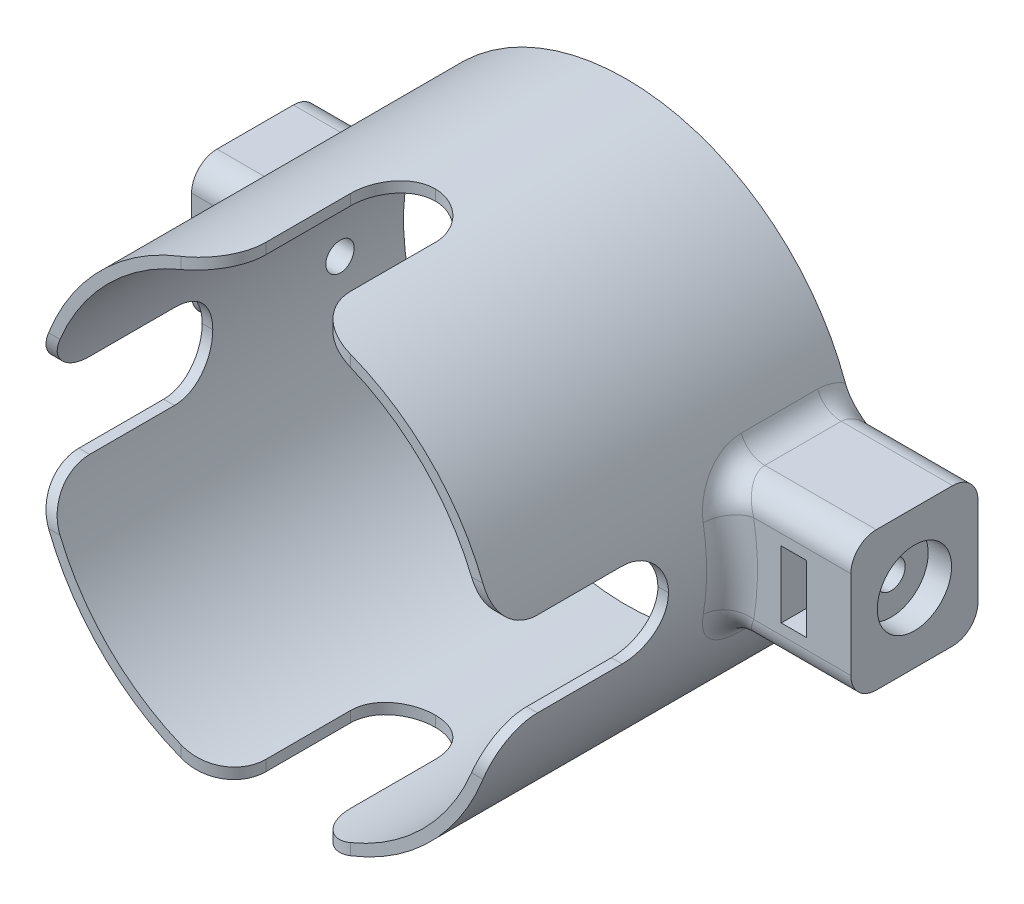
SolidWorks part; units mm, degrees
ref_plane "Front Plane" through (0, 0, 0) normal (0, 0, 1) x (1, 0, 0)
ref_plane "Top Plane" through (0, 0, 0) normal (0, 1, 0) x (1, 0, 0)
ref_plane "Right Plane" through (0, 0, 0) normal (1, 0, 0) x (0, 0, -1)
sketch "Sketch2" plane through (0, 0, 0) normal (0, 0, 1) x (1, 0, 0)
  circle A0 centre (0, 0) radius 66.675
  circle A1 centre (0, 0) radius 69.85
  dimension "D1" = 133.35
  dimension "D2" = 139.7
extrude "Boss-Extrude1" add sketch "Sketch2" along normal mid plane 177.8
sketch "Sketch6" plane through (0, 0, 0) normal (0, 0, 1) x (1, 0, 0)
  line L0 (66.675, -20.8199) -> (66.675, 20.8199)
  line L1 (66.675, 20.8199) -> (92.075, 20.8199)
  line L2 (92.075, 20.8199) -> (92.075, -20.8199)
  line L3 (92.075, 0) -> (66.675, 0) construction
  line L4 (66.675, -20.8199) -> (92.075, -20.8199)
  line L5 (0, 0) -> (0, 66.675) construction
  line L6 (-66.675, 20.8199) -> (-92.075, 20.8199)
  line L7 (-66.675, -20.8199) -> (-66.675, 20.8199)
  line L8 (-66.675, -20.8199) -> (-92.075, -20.8199)
  line L9 (-92.075, 20.8199) -> (-92.075, -20.8199)
  circle A0 centre (0, 0) radius 66.675 construction
  circle A1 centre (0, 0) radius 69.85 construction
  dimension "D1" = 25.4
extrude "Boss-Extrude2" add sketch "Sketch6" along normal mid plane 38.1
sketch "Sketch12" plane through (92.075, 0, 0) normal (1, 0, 0) x (0, 0, -1)
  line L1 (-19.05, 20.8199) -> (-19.05, -20.8199) construction
  line L4 (-19.05, 10) -> (19.05, 10)
  line L5 (19.05, -20.8199) -> (19.05, 20.8199) construction
  line L6 (19.05, 10) -> (19.05, -10)
  line L7 (19.05, -10) -> (-19.05, -10)
  line L8 (0, 10) -> (0, -10) construction
  line L9 (-19.05, 10) -> (-19.05, -10)
  dimension "D1" = 20
extrude "Cut-Extrude1" cut sketch "Sketch12" against normal blind 7.5
sketch "Sketch17" plane through (92.075, 0, 0) normal (1, 0, 0) x (0, 0, -1)
  line L0 (-19.05, 20.8199) -> (19.05, 20.8199)
  line L1 (19.05, 20.8199) -> (19.05, -20.8199)
  line L2 (19.05, -20.8199) -> (-19.05, -20.8199)
  line L3 (-19.05, -20.8199) -> (-19.05, 20.8199)
extrude "Boss-Extrude5" add sketch "Sketch17" along normal blind 6.35
sketch "Sketch18" plane through (98.425, 0, 0) normal (1, 0, 0) x (0, 0, -1)
  line L4 (-19.05, 20.8199) -> (-19.05, -20.8199)
  line L5 (-19.05, -20.8199) -> (19.05, -20.8199)
  line L6 (19.05, -20.8199) -> (19.05, 20.8199)
  line L7 (19.05, 20.8199) -> (-19.05, 20.8199)
  line L8 (-19.05, 20.8199) -> (-19.05, -20.8199)
  line L9 (-19.05, -20.8199) -> (19.05, -20.8199)
  line L10 (19.05, -20.8199) -> (19.05, 20.8199)
  line L11 (19.05, 20.8199) -> (-19.05, 20.8199)
  circle A0 centre (0, 0) radius 11.125
  dimension "D1" = 22.25
  dimension "D2" = 0
extrude "Boss-Extrude6" add sketch "Sketch18" along normal blind 7
sketch "Sketch19" plane through (0, 0, 0) normal (1, 0, 0) x (0, 0, -1)
  circle A0 centre (0, 0) radius 4.25
  dimension "D1" = 8.5
extrude "Cut-Extrude5" cut sketch "Sketch19" against normal through all both and the other way through all
mirror "Mirror6" [suppressed] about plane through (0, 0, 0) normal (1, 0, 0)
fillet "Fillet3" radius 7.62 16 edges at (66.675, -20.8199, 0) (69.85, 0, -19.05) (66.675, 20.8199, 0) (69.85, 0, 19.05) (-69.85, 0, -19.05) (-66.675, -20.8199, 0) (-69.85, 0, 19.05) (-66.675, 20.8199, 0) (86.05, -20.8199, 19.05) (86.05, -20.8199, -19.05) (86.05, 20.8199, -19.05) (86.05, 20.8199, 19.05) (-79.375, 20.8199, 19.05) (-79.375, -20.8199, 19.05) (-79.375, -20.8199, -19.05) (-79.375, 20.8199, -19.05)
sketch "Sketch21" plane through (0, 0, 0) normal (1, 0, 0) x (0, 0, -1)
  line L0 (88.9, 0) -> (0, 0) construction
  line L1 (88.9, -66.675) -> (88.9, 66.675) construction
  line L2 (88.9, -12.7) -> (88.9, 12.7)
  line L3 (88.9, 12.7) -> (38.1, 12.7)
  line L4 (38.1, 12.7) -> (38.1, -12.7)
  line L5 (88.9, -12.7) -> (38.1, -12.7)
  point P10 (38.1, 0)
  dimension "D1" = 12.7
  dimension "D2" = 50.8
extrude "Cut-Extrude6" cut sketch "Sketch21" against normal through all both and the other way through all
mirror "Mirror7" about plane through (0, 0, 0) normal (0, 0, 1) of "Cut-Extrude6"
pattern_circular "CirPattern5" count 4 over 360 about axis through (0, 0, 88.9) along (0, 0, 1) of "Mirror7"
sketch "Sketch22" plane through (0, 0, 0) normal (0, 0, 1) x (1, 0, 0)
  line L0 (-72.8196, 77.1078) -> (-72.8196, -78.4024)
  line L1 (-72.8196, -78.4024) -> (114.8931, -78.4024)
  line L2 (114.8931, -78.4024) -> (114.8931, 77.1078)
  line L3 (114.8931, 77.1078) -> (-72.8196, 77.1078)
extrude "Cut-Extrude7" [suppressed] cut sketch "Sketch22" against normal through all both and the other way through all
sketch "Sketch23" plane through (0, 0, 0) normal (1, 0, 0) x (0, 0, -1)
  line L1 (-35, 87.107) -> (35, 87.107)
  line L2 (-35, 87.107) -> (-35, -87.107)
  line L3 (-35, -87.107) -> (35, -87.107)
  line L4 (35, 87.107) -> (35, -87.107)
  line L5 (-35, 87.107) -> (35, -87.107) construction
  line L6 (-35, -87.107) -> (35, 87.107) construction
  point P0 (0, 0)
  dimension "D1" = 70
extrude "Cut-Extrude8" [suppressed] cut sketch "Sketch23" against normal through all both and the other way through all flip side to cut
sketch "Sketch25" plane through (0, 0, 0) normal (0, 0, 1) x (1, 0, 0)
  line L1 (49.3489, 42.9422) -> (126.5756, 42.9422)
  line L2 (49.3489, 42.9422) -> (49.3489, -42.9422)
  line L3 (49.3489, -42.9422) -> (126.5756, -42.9422)
  line L4 (126.5756, 42.9422) -> (126.5756, -42.9422)
  line L5 (49.3489, 42.9422) -> (126.5756, -42.9422) construction
  line L6 (49.3489, -42.9422) -> (126.5756, 42.9422) construction
  point P0 (87.9623, 0)
extrude "Cut-Extrude9" [suppressed] cut sketch "Sketch25" against normal through all both and the other way through all flip side to cut
sketch "Sketch26" plane through (0, 0, 0) normal (0, 0, 1) x (1, 0, 0)
  line L0 (-92.075, 20.8199) -> (-87.0713, 20.8199)
  line L1 (-92.075, 20.8199) -> (-72.0609, 20.8199) construction
  line L2 (-87.0713, 20.8199) -> (-87.0713, -20.8199)
  line L3 (-72.0609, -20.8199) -> (-92.075, -20.8199) construction
  line L4 (-87.0713, -20.8199) -> (-92.075, -20.8199)
  line L5 (-92.075, -20.8199) -> (-92.075, 20.8199)
extrude "Cut-Extrude10" [suppressed] cut sketch "Sketch26" against normal through all both and the other way through all
sketch "Sketch27" plane through (-92.075, 0, 0) normal (-1, 0, 0) x (0, 0, 1)
  circle A0 centre (0, 0) radius 10.5 construction
  circle A1 centre (0, 10.5) radius 1.5
  circle A2 centre (10.5, 0) radius 1.5
  circle A3 centre (0, -10.5) radius 1.5
  circle A4 centre (-10.5, 0) radius 1.5
  dimension "D1" = 21
  dimension "D2" = 3
extrude "Cut-Extrude11" cut sketch "Sketch27" against normal blind 20
ref_plane "Plane1" through (0, 0, -25.4) normal (0, 0, -1) x (-1, 0, 0)
sketch "Sketch29" plane through (0, 0, 0) normal (0, 1, 0) x (1, 0, 0)
  line L5 (0, 38.1) -> (0, 88.9) construction
  line L6 (12.7, 38.1) -> (-12.7, 38.1) construction
  line L7 (-12.7, 88.9) -> (-68.6858, 88.9) construction
  line L8 (76.3372, 19.05) -> (105.425, 19.05) construction
  line L9 (-81.4906, 107.95) -> (81.4906, 107.95)
  line L10 (-81.4906, 107.95) -> (-81.4906, 19.05)
  line L11 (-81.4906, 19.05) -> (81.4906, 19.05)
  line L12 (81.4906, 107.95) -> (81.4906, 19.05)
  line L13 (-81.4906, 107.95) -> (81.4906, 19.05) construction
  line L14 (-81.4906, 19.05) -> (81.4906, 107.95) construction
  point P9 (0, 63.5)
extrude "Cut-Extrude12" cut sketch "Sketch29" against normal through all both and the other way through all
fillet "Fillet4" radius 12.7 16 edges at (67.07, -12.7, 88.9) (67.07, -12.7, 38.1) (67.07, 12.7, 38.1) (67.07, 12.7, 88.9) (12.7, -67.07, 88.9) (-12.7, -67.07, 88.9) (12.7, -67.07, 38.1) (-12.7, -67.07, 38.1) (-67.07, 12.7, 38.1) (-67.07, -12.7, 38.1) (12.7, 67.07, 88.9) (-12.7, 67.07, 88.9) (-12.7, 67.07, 38.1) (12.7, 67.07, 38.1) (-67.07, -12.7, 88.9) (-67.07, 12.7, 88.9)
sketch "Sketch33" plane through (0, 0, -19.05) normal (0, 0, -1) x (-1, 0, 0)
  line L0 (84.2061, 13.1999) -> (84.2061, -13.1999) construction
  line L1 (92.075, 13.1999) -> (76.3372, 13.1999) construction
  line L2 (76.3372, -13.1999) -> (92.075, -13.1999) construction
  line L6 (-84.575, 0) -> (-72.0609, 0) construction
  line L7 (-84.575, -10) -> (-84.575, 10) construction
  line L8 (-72.0609, 0) -> (-72.0609, 20.8199) construction
  line L9 (72.0609, 20.8199) -> (72.0609, 0) construction
  line L10 (72.0609, 0) -> (84.2061, 0) construction
  circle A0 centre (84.2061, 0) radius 1.75
  circle A2 centre (-78.318, 0) radius 1.75
  dimension "D1" = 3.5
extrude "Cut-Extrude13" cut sketch "Sketch33" against normal blind 10
